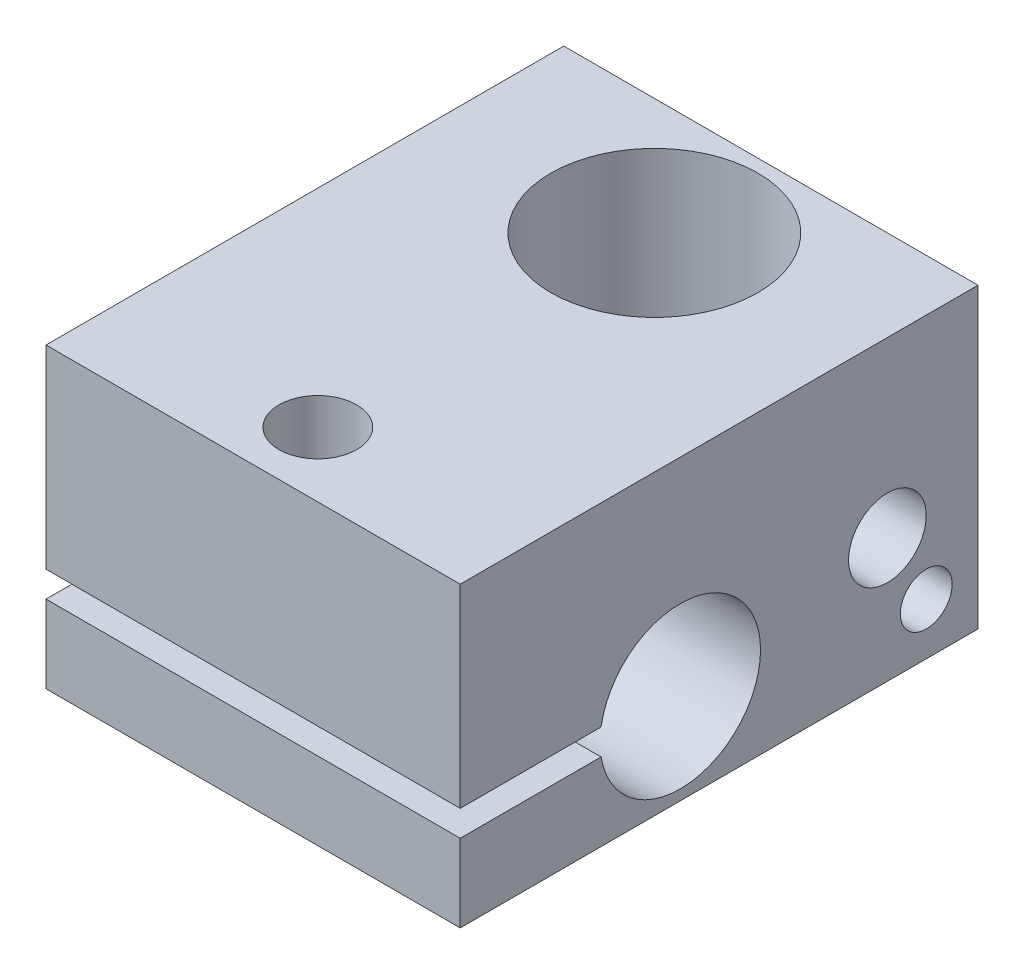
SolidWorks part; units mm, degrees
ref_plane "정면" through (0, 0, 0) normal (0, 0, 1) x (1, 0, 0)
ref_plane "윗면" through (0, 0, 0) normal (0, 1, 0) x (1, 0, 0)
ref_plane "우측면" through (0, 0, 0) normal (1, 0, 0) x (0, 0, -1)
sketch "스케치1" plane through (0, 0, 0) normal (1, 0, 0) x (0, 0, -1)
  line L1 (0, 0) -> (20, 0)
  line L2 (0, 0) -> (0, 11.5)
  line L3 (0, 11.5) -> (20, 11.5)
  line L4 (20, 0) -> (20, 11.5)
  dimension "D1" = 20
  dimension "D2" = 11.5
extrude "보스-돌출1" add sketch "스케치1" along normal blind 16
sketch "스케치2" plane through (0, 11.5, 0) normal (0, 1, 0) x (1, 0, 0)
  line L0 (0, 15.5) -> (16, 15.5) construction
  line L1 (0, 20) -> (0, 0) construction
  line L2 (16, 20) -> (16, 0) construction
  line L3 (0, 2.5) -> (16, 2.5) construction
  line L4 (8, 20) -> (8, 0) construction
  line L5 (16, 20) -> (0, 20) construction
  line L6 (16, 0) -> (0, 0) construction
  circle A0 centre (8, 2.5) radius 1.5
  circle A1 centre (8, 15.5) radius 4
  dimension "D2" = 8
  dimension "D4" = 3
  dimension "D1" = 17.5
  dimension "D3" = 4.5
extrude "컷-돌출1" cut sketch "스케치2" against normal through all contours A0 | A1 region at (8, 11.5, -2.5) region at (8, 11.5, -15.5)
sketch "스케치6" plane through (16, 0, 0) normal (1, 0, 0) x (0, 0, -1)
  line L0 (20, 0) -> (20, 11.5) construction
  line L1 (0, 0) -> (20, 0) construction
  line L2 (8.5, 4) -> (0, 4)
  line L3 (8.5, 3) -> (0, 3)
  line L4 (0, 11.5) -> (0, 0) construction
  line L5 (8.5, 3.5) -> (0, 3.5)
  line L6 (8.5, 4) -> (8.5, 3)
  line L7 (0, 4) -> (0, 3)
  circle A0 centre (8.5, 3.5) radius 3.1
  circle A1 centre (16.5, 4.8) radius 1.5
  circle A2 centre (18, 2) radius 1
  line M4 (0, 11.5) -> (0, 0)
  dimension "D1" = 6.2
  dimension "D4" = 3
  dimension "D5" = 2
  dimension "D2" = 11.5
  dimension "D3" = 3.5
  dimension "D6" = 3.5
  dimension "D7" = 4.8
  dimension "D8" = 2
  dimension "D9" = 2
  dimension "D10" = 0.5
  dimension "D11" = 0.5
extrude "컷-돌출2" cut sketch "스케치6" against normal blind 2 contours A2 region at (16, 2, -18)
extrude "컷-돌출3" cut sketch "스케치6<3>" against normal blind 3.8 contours A1 region at (16, 4.8, -16.5)
sketch "스케치6<3>" plane through (16, 0, 0) normal (1, 0, 0) x (0, 0, -1) same geometry as "스케치6"
extrude "컷-돌출4" cut sketch "스케치6<4>" against normal through all contours A0 | A0 L2 L5 M4 | A0 L5 L3 M4 | L5 A0 L3 L6 | L2 A0 L5 L6 region at (16, 3.7495, -6.9567) region at (16, 3.5, -8.6757) region at (16, 3.7503, -2.7068) region at (16, 3.2505, -6.9567) region at (16, 3.2497, -2.7068)
sketch "스케치6<4>" plane through (16, 0, 0) normal (1, 0, 0) x (0, 0, -1) same geometry as "스케치6"
